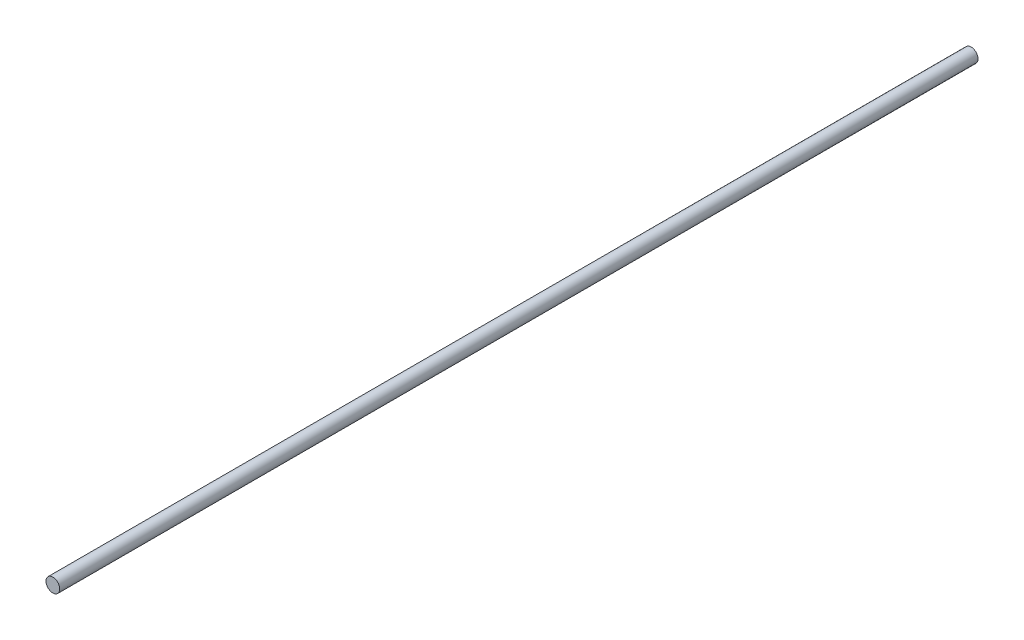
SolidWorks part; units mm, degrees
ref_plane "Front Plane" through (0, 0, 0) normal (0, 0, 1) x (1, 0, 0)
ref_plane "Top Plane" through (0, 0, 0) normal (0, 1, 0) x (1, 0, 0)
ref_plane "Right Plane" through (0, 0, 0) normal (1, 0, 0) x (0, 0, -1)
sketch "Sketch2" plane through (0, 0, 0) normal (0, 0, 1) x (1, 0, 0)
  circle A0 centre (0, 0) radius 1.5
  dimension "D1" = 3
extrude "Boss-Extrude1" add sketch "Sketch2" along normal blind 200
